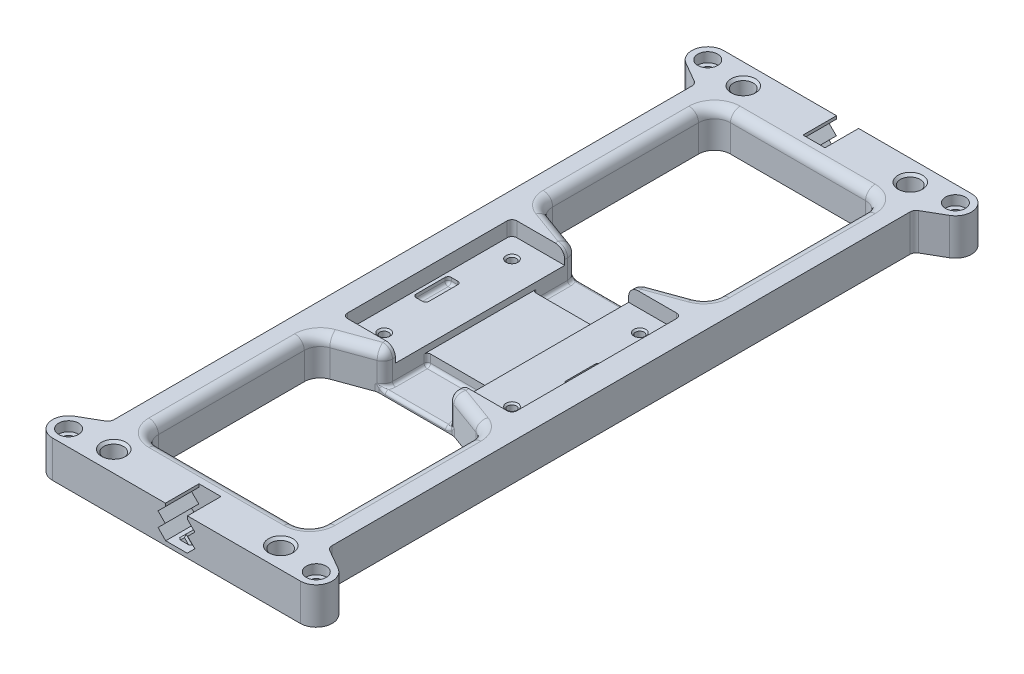
SolidWorks part; units mm, degrees
ref_plane "Front Plane" through (0, 0, 0) normal (0, 0, 1) x (1, 0, 0)
ref_plane "Top Plane" through (0, 0, 0) normal (0, 1, 0) x (1, 0, 0)
ref_plane "Right Plane" through (0, 0, 0) normal (1, 0, 0) x (0, 0, -1)
sketch "Sketch1" plane through (0, 0, 0) normal (0, 1, 0) x (1, 0, 0)
  line L0 (0, 0) -> (0, 90) construction
  line L1 (34.125, 90) -> (-34.125, 90) construction
  line L2 (-34.125, 90) -> (-34.125, 0)
  line L3 (-34.125, 0) -> (34.125, 0)
  line L4 (-34.125, 90) -> (-34.125, 103)
  line L5 (-32.125, 105) -> (32.125, 105)
  line L6 (0, 105) -> (0, 90) construction
  line L7 (34.125, 90) -> (34.125, 103)
  line L8 (34.125, 90) -> (34.125, 0)
  line L14 (-34.125, 93) -> (34.125, 93) construction
  circle A1 centre (-26.125, 98.5) radius 3.075 construction
  circle A2 centre (26.125, 98.5) radius 3.075 construction
  arc A10 (34.125, 103) -> (32.125, 105) centre (32.125, 103) ccw
  arc A11 (-34.125, 103) -> (-32.125, 105) centre (-32.125, 103) cw
  point P42 (34.125, 105)
  point P45 (-34.125, 105)
  dimension "D3" = 6.15
  dimension "D4" = 2
  dimension "D1" = 34.125
  dimension "D2" = 90
  dimension "D6" = 8
  dimension "D7" = 8.5
  dimension "D8" = 12
  dimension "D9" = 3
  dimension "D11" = 105
extrude "Boss-Extrude1" add sketch "Sketch1" along normal blind 11.5
sketch "Sketch3" plane through (0, 11.5, 0) normal (0, 1, 0) x (1, 0, 0)
  line L0 (0, 0) -> (-34.125, 0) construction
  line L2 (0, 0) -> (0, 105) construction
  line L3 (32.125, 105) -> (-32.125, 105) construction
  line L4 (3.96, -16.3) -> (3.96, 16.3)
  line L5 (-2.46, -17.8) -> (2.46, -17.8)
  line L6 (-3.96, 16.3) -> (-3.96, -16.3)
  line L7 (2.46, 17.8) -> (-2.46, 17.8)
  line L8 (0, 17.8) -> (0, -17.8) construction
  arc A0 (-2.46, 17.8) -> (-3.96, 16.3) centre (-2.46, 16.3) ccw
  arc A1 (3.96, 16.3) -> (2.46, 17.8) centre (2.46, 16.3) ccw
  arc A2 (2.46, -17.8) -> (3.96, -16.3) centre (2.46, -16.3) ccw
  arc A3 (-3.96, -16.3) -> (-2.46, -17.8) centre (-2.46, -16.3) ccw
  point P9 (0, 0)
  point P23 (0, 0)
  dimension "D2" = 1.5
  dimension "D1" = 35.6
  dimension "D3" = 7.92
sketch "Sketch4" plane through (0, 11.5, 0) normal (0, 1, 0) x (1, 0, 0)
  circle A2 centre (26.125, 98.5) radius 3.075 construction
  circle A5 centre (-26.125, 98.5) radius 3.075 construction
  circle A10 centre (26.125, 98.5) radius 3.075
  circle A13 centre (-26.125, 98.5) radius 3.075
extrude "Cut-Extrude1" cut sketch "Sketch4" against normal blind 6
sketch "Sketch41" plane through (0, 0, -105) normal (0, 0, -1) x (-1, 0, 0)
  line L0 (5.55, 3.75) -> (3.3, 6) construction
  line L1 (5.55, 3.75) -> (3.3, 1.5) construction
  line L2 (0, 11.5) -> (0, 1.5) construction
  line L3 (0, 1.5) -> (3.3, 1.5) construction
  line L4 (3.3, 6) -> (5.55, 8.25) construction
  line L5 (3.3, 6) -> (3.3, 1.5) construction
  line L6 (5.55, 8.25) -> (3.3, 10.5) construction
  line L7 (3.3, 6) -> (3.3, 10.5) construction
  line L8 (5.55, 3.75) -> (5.55, 8.25) construction
  line L9 (3.3, 10.5) -> (3.3, 11.5) construction
  line L10 (3.3, 1.5) -> (5.55, 1.5) construction
  line L11 (5.55, 1.5) -> (5.55, 3.75) construction
  line L12 (5.55, 3.75) -> (3.3, 3.75) construction
  line L13 (5.55, 8.25) -> (3.3, 8.25) construction
  line L14 (3.3, 6) -> (5.55, 6) construction
  line L15 (-3.3, 11.5) -> (3.3, 11.5)
  line L16 (3.3621, 1.35) -> (-3.3621, 1.35)
  line L17 (0, 1.35) -> (0, 1.5) construction
  line L18 (-3.3, 11.5) -> (-3.45, 11.5)
  line L19 (-3.45, 10.5621) -> (-3.45, 11.5)
  line L20 (3.45, 10.5621) -> (3.45, 11.5)
  line L21 (5.7621, 8.25) -> (3.45, 10.5621)
  line L22 (3.5121, 6) -> (5.7621, 8.25)
  line L23 (5.7621, 3.75) -> (3.5121, 6)
  line L24 (5.7621, 3.75) -> (3.3621, 1.35)
  line L25 (3.3, 11.5) -> (3.45, 11.5)
  line L26 (-5.7621, 8.25) -> (-3.45, 10.5621)
  line L27 (-3.5121, 6) -> (-5.7621, 8.25)
  line L28 (-5.7621, 3.75) -> (-3.5121, 6)
  line L29 (-5.7621, 3.75) -> (-3.3621, 1.35)
  line L30 (-32.125, 11.5) -> (32.125, 11.5) construction
  dimension "D1" = 1
  dimension "D2" = 45
  dimension "D3" = 45
  dimension "D4" = 45
  dimension "D5" = 45
  dimension "D6" = 3.3
  dimension "D7" = 10
  dimension "D8" = 0.15
  dimension "D9" = 0.15
  dimension "D10" = 0.15
  dimension "D11" = 0.15
  dimension "D12" = 0.15
  dimension "D13" = 0.15
extrude "Cut-Extrude31" cut sketch "Sketch41" against normal blind 10.5
sketch "Sketch42" plane through (0, 0, -94.5) normal (0, 0, -1) x (-1, 0, 0)
  line L0 (0, 1.35) -> (0, 3.35) construction
  line L1 (-3.3621, 1.35) -> (3.3621, 1.35) construction
  line L2 (0, 3.35) -> (2, 1.35)
  line L3 (2, 1.35) -> (-2, 1.35)
  line L4 (0, 3.35) -> (-2, 1.35)
  dimension "D1" = 45
  dimension "D2" = 2
extrude "Boss-Extrude9" add sketch "Sketch42" along normal blind 8
chamfer "Chamfer7" distance 0.5 angle 45 2 edges at (1, 2.35, -102.5) (-1, 2.35, -102.5)
mirror "Mirror1" about plane through (-34.125, 11.5, 0) normal (0, 0, -1) of "Boss-Extrude1", "Cut-Extrude1", "Cut-Extrude31", "Boss-Extrude9", "Chamfer7"
sketch "Sketch28" plane through (0, 11.5, 0) normal (0, 1, 0) x (1, 0, 0)
  line L1 (-26, 26) -> (26, 26) construction
  line L2 (-26, 26) -> (-26, -26) construction
  line L3 (-26, -26) -> (26, -26) construction
  line L4 (26, 26) -> (26, -26) construction
  line L5 (-26, 26) -> (26, -26) construction
  line L6 (-26, -26) -> (26, 26) construction
  line L7 (-25, 26.5) -> (25, 26.5)
  line L8 (-26.5, 25) -> (-26.5, -25)
  line L9 (-25, -26.5) -> (25, -26.5)
  line L10 (26.5, 25) -> (26.5, -25)
  line L11 (-26.5, 26.5) -> (26.5, -26.5) construction
  line L12 (-26.5, -26.5) -> (26.5, 26.5) construction
  arc A0 (-25, -26.5) -> (-26.5, -25) centre (-25, -25) cw
  arc A1 (25, -26.5) -> (26.5, -25) centre (25, -25) ccw
  arc A2 (25, 26.5) -> (26.5, 25) centre (25, 25) cw
  arc A3 (-25, 26.5) -> (-26.5, 25) centre (-25, 25) ccw
  point P0 (0, 0)
  point P6 (0, 0)
  dimension "D4" = 1.5
  dimension "D1" = 52
  dimension "D2" = 0.5
  dimension "D3" = 0.5
extrude "Cut-Extrude21" cut sketch "Sketch28" against normal blind 4.6
sketch "Sketch36" plane through (0, 6.9, 0) normal (0, 1, 0) x (1, 0, 0)
  line L2 (-26, 26) -> (-26, -26) construction
  line L3 (-26, 26) -> (26, 26) construction
  circle A0 centre (-20, 20) radius 1.35
  circle A1 centre (20, 20) radius 1.35
  circle A2 centre (20, -20) radius 1.35
  circle A3 centre (-20, -20) radius 1.35
  point P15 (0, 0)
  dimension "D3" = 2.7
  dimension "D1" = 6
  dimension "D2" = 6
  dimension "D4" = 4
extrude "Cut-Extrude28" cut sketch "Sketch36" against normal blind 5
chamfer "Chamfer6" distance 0.5 angle 45 4 edges at (-20, 6.9, 21.35) (20, 6.9, 21.35) (20, 6.9, -18.65) (-20, 6.9, -18.65)
sketch "Sketch29" plane through (0, 6.9, 0) normal (0, 1, 0) x (1, 0, 0)
  line L0 (0, 0) -> (26.5, 0) construction
  line L5 (0, 0) -> (0, -26.5) construction
  line L6 (-25, -26.5) -> (25, -26.5) construction
  line L7 (26.5, -25) -> (26.5, 25) construction
  line L8 (-10, 26.5) -> (10, 16.5) construction
  line L9 (-10, 16.5) -> (10, 26.5) construction
  line L10 (-10, -16.5) -> (10, -16.5)
  line L11 (-10, -16.5) -> (-10, -26.5)
  line L12 (-10, -26.5) -> (10, -26.5)
  line L13 (10, -16.5) -> (10, -26.5)
  line L14 (-10, -16.5) -> (10, -26.5) construction
  line L15 (-10, -26.5) -> (10, -16.5) construction
  line L16 (10, 16.5) -> (10, 26.5)
  line L17 (-10, 26.5) -> (10, 26.5)
  line L18 (-10, 16.5) -> (-10, 26.5)
  line L19 (-10, 16.5) -> (10, 16.5)
  point P4 (0, -21.5)
  point P17 (0, 21.5)
  dimension "D1" = 20
  dimension "D2" = 10
extrude "Cut-Extrude22" cut sketch "Sketch29" against normal blind 5.5
sketch "Sketch25" plane through (0, 0, 0) normal (0, -1, 0) x (1, 0, 0)
  line L0 (0, 0) -> (34.125, 0) construction
  line L1 (34.125, 103) -> (34.125, -103) construction
  line L2 (0, 0) -> (0, 105) construction
  line L4 (41.25, 95.6699) -> (35.125, 92.1336)
  line L5 (38.75, 100) -> (34.125, 100) construction
  line L6 (34.125, 90.4016) -> (34.125, 103)
  line L8 (32.125, 105) -> (38.75, 105)
  line L9 (-38.75, 100) -> (-34.125, 100) construction
  line L10 (-32.125, 105) -> (-38.75, 105)
  line L11 (-34.125, 90.4016) -> (-34.125, 103)
  line L12 (-41.25, 95.6699) -> (-35.125, 92.1336)
  line L13 (-38.75, -100) -> (-34.125, -100) construction
  line L14 (38.75, -100) -> (34.125, -100) construction
  line L15 (-41.25, -95.6699) -> (-35.125, -92.1336)
  line L16 (-34.125, -90.4016) -> (-34.125, -103)
  line L17 (-32.125, -105) -> (-38.75, -105)
  line L18 (32.125, -105) -> (38.75, -105)
  line L19 (34.125, -90.4016) -> (34.125, -103)
  line L20 (41.25, -95.6699) -> (35.125, -92.1336)
  line L21 (32.125, 105) -> (-32.125, 105) construction
  circle A0 centre (38.75, 100) radius 1.7
  arc A1 (41.25, 95.6699) -> (38.75, 105) centre (38.75, 100) ccw
  arc A2 (35.125, 92.1336) -> (34.125, 90.4016) centre (36.125, 90.4016) ccw
  arc A17 (34.125, 103) -> (32.125, 105) centre (32.125, 103) ccw
  arc A18 (-34.125, 103) -> (-32.125, 105) centre (-32.125, 103) cw
  arc A19 (-35.125, 92.1336) -> (-34.125, 90.4016) centre (-36.125, 90.4016) cw
  arc A20 (-41.25, 95.6699) -> (-38.75, 105) centre (-38.75, 100) cw
  circle A21 centre (-38.75, 100) radius 1.7
  circle A22 centre (-38.75, -100) radius 1.7
  arc A23 (-41.25, -95.6699) -> (-38.75, -105) centre (-38.75, -100) ccw
  arc A24 (-35.125, -92.1336) -> (-34.125, -90.4016) centre (-36.125, -90.4016) ccw
  arc A25 (-34.125, -103) -> (-32.125, -105) centre (-32.125, -103) ccw
  arc A26 (34.125, -103) -> (32.125, -105) centre (32.125, -103) cw
  arc A27 (35.125, -92.1336) -> (34.125, -90.4016) centre (36.125, -90.4016) cw
  arc A28 (41.25, -95.6699) -> (38.75, -105) centre (38.75, -100) cw
  circle A29 centre (38.75, -100) radius 1.7
  arc A30 (34.125, 103) -> (32.125, 105) centre (32.125, 103) ccw construction
  dimension "D1" = 3.4
  dimension "D2" = 10
  dimension "D6" = 2
  dimension "D3" = 4.625
  dimension "D5" = 60
extrude "Boss-Extrude7" add sketch "Sketch25" against normal up to surface (11.5 mm away) up to face at (0, 11.5, 0)
sketch "Sketch27" plane through (0, 11.5, 0) normal (0, 1, 0) x (1, 0, 0)
  circle A4 centre (-38.75, -100) radius 3.1
  circle A5 centre (38.75, -100) radius 3.1
  circle A6 centre (-38.75, 100) radius 3.1
  circle A7 centre (38.75, 100) radius 3.1
  dimension "D1" = 6.2
extrude "Cut-Extrude20" cut sketch "Sketch27" against normal blind 3
sketch "Sketch37" plane through (0, 6.9, 0) normal (0, 1, 0) x (1, 0, 0)
  line L0 (34.125, 0) -> (0, 0) construction
  line L1 (34.125, -90.4016) -> (34.125, 90.4016) construction
  line L2 (0, 0) -> (-34.125, 0) construction
  line L3 (26.5, -25) -> (26.5, 25) construction
  line L4 (24.5, 5.5) -> (22.5, 5.5)
  line L5 (25.5, 4.5) -> (25.5, -4.5)
  line L6 (24.5, -5.5) -> (22.5, -5.5)
  line L7 (21.5, 4.5) -> (21.5, -4.5)
  line L8 (25.5, 5.5) -> (21.5, -5.5) construction
  line L9 (25.5, -5.5) -> (21.5, 5.5) construction
  line L10 (0, 0) -> (0, 26.5) construction
  line L11 (-10, 16.5) -> (10, 16.5) construction
  line L12 (-24.5, -5.5) -> (-22.5, -5.5)
  line L13 (-25.5, 4.5) -> (-25.5, -4.5)
  line L14 (-24.5, 5.5) -> (-22.5, 5.5)
  line L15 (-21.5, 4.5) -> (-21.5, -4.5)
  line L21 (10, 16.5) -> (10, -16.5)
  line L23 (25, 26.5) -> (-25, 26.5) construction
  line L24 (-10, 16.5) -> (10, 16.5)
  line L25 (-10, 16.5) -> (-10, -16.5)
  line L26 (-10, -16.5) -> (10, -16.5)
  arc A0 (22.5, -5.5) -> (21.5, -4.5) centre (22.5, -4.5) cw
  arc A1 (25.5, -4.5) -> (24.5, -5.5) centre (24.5, -4.5) cw
  arc A2 (22.5, 5.5) -> (21.5, 4.5) centre (22.5, 4.5) ccw
  arc A3 (24.5, 5.5) -> (25.5, 4.5) centre (24.5, 4.5) cw
  arc A4 (-22.5, 5.5) -> (-21.5, 4.5) centre (-22.5, 4.5) cw
  arc A5 (-24.5, 5.5) -> (-25.5, 4.5) centre (-24.5, 4.5) ccw
  arc A6 (-22.5, -5.5) -> (-21.5, -4.5) centre (-22.5, -4.5) ccw
  arc A7 (-25.5, -4.5) -> (-24.5, -5.5) centre (-24.5, -4.5) ccw
  point P5 (23.5, 0)
  point P54 (10, 0)
  point P56 (-10, 0)
  dimension "D4" = 1
  dimension "D1" = 11
  dimension "D2" = 4
  dimension "D3" = 3
extrude "Cut-Extrude29" cut sketch "Sketch37" against normal blind 2
fillet "Fillet20" radius 1 16 edges at (25.2071, 4.9, -5.2071) (25.5, 4.9, 0) (25.2071, 4.9, 5.2071) (23.5, 4.9, 5.5) (21.7929, 4.9, 5.2071) (21.5, 4.9, 0) (21.7929, 4.9, -5.2071) (-21.7929, 4.9, -5.2071) (-21.5, 4.9, 0) (-21.7929, 4.9, 5.2071) (-23.5, 4.9, 5.5) (-25.2071, 4.9, 5.2071) (-25.5, 4.9, 0) (-25.2071, 4.9, -5.2071) (23.5, 4.9, -5.5) (-23.5, 4.9, -5.5)
sketch "Sketch38" plane through (0, 11.5, 0) normal (0, 1, 0) x (1, 0, 0)
  line L0 (11.9739, -30.2185) -> (22.8351, -34.1716)
  line L1 (26.125, -38.8701) -> (26.125, -84.5)
  line L2 (21.125, -89.5) -> (-21.125, -89.5)
  line L3 (0, -89.5) -> (0, -26.5) construction
  line L4 (-10, -26.5) -> (10, -26.5) construction
  line L6 (34.125, -90.4016) -> (34.125, 90.4016) construction
  line L7 (-3.45, -94.5) -> (3.45, -94.5) construction
  line L9 (-25, -26.5) -> (25, -26.5) construction
  line L12 (0, 0) -> (34.125, 0) construction
  line L13 (0, 89.5) -> (0, 26.5) construction
  line L20 (10, -27.3994) -> (10, -26.5)
  line L21 (10, -26.5) -> (25, -26.5) construction
  line L22 (10, -26.5) -> (-10, -26.5)
  line L23 (10, -26.5) -> (10, 26.5) construction
  line L24 (-10, -27.3994) -> (-10, -26.5)
  line L25 (-26.125, -38.8701) -> (-26.125, -84.5)
  line L26 (-11.9739, -30.2185) -> (-22.8351, -34.1716)
  line L27 (-11.9739, 30.2185) -> (-22.8351, 34.1716)
  line L28 (-26.125, 38.8701) -> (-26.125, 84.5)
  line L29 (-10, 27.3994) -> (-10, 26.5)
  line L30 (10, 26.5) -> (-10, 26.5)
  line L31 (10, 27.3994) -> (10, 26.5)
  line L32 (21.125, 89.5) -> (-21.125, 89.5)
  line L33 (26.125, 38.8701) -> (26.125, 84.5)
  line L34 (11.9739, 30.2185) -> (22.8351, 34.1716)
  arc A0 (26.125, -38.8701) -> (22.8351, -34.1716) centre (21.125, -38.8701) ccw
  arc A1 (26.125, -84.5) -> (21.125, -89.5) centre (21.125, -84.5) cw
  arc A8 (11.9739, -30.2185) -> (10, -27.3994) centre (13, -27.3994) cw
  arc A9 (-11.9739, -30.2185) -> (-10, -27.3994) centre (-13, -27.3994) ccw
  arc A10 (-26.125, -84.5) -> (-21.125, -89.5) centre (-21.125, -84.5) ccw
  arc A11 (-26.125, -38.8701) -> (-22.8351, -34.1716) centre (-21.125, -38.8701) cw
  arc A12 (-26.125, 38.8701) -> (-22.8351, 34.1716) centre (-21.125, 38.8701) ccw
  arc A13 (-26.125, 84.5) -> (-21.125, 89.5) centre (-21.125, 84.5) cw
  arc A14 (-11.9739, 30.2185) -> (-10, 27.3994) centre (-13, 27.3994) cw
  arc A15 (11.9739, 30.2185) -> (10, 27.3994) centre (13, 27.3994) ccw
  arc A16 (26.125, 84.5) -> (21.125, 89.5) centre (21.125, 84.5) ccw
  arc A17 (26.125, 38.8701) -> (22.8351, 34.1716) centre (21.125, 38.8701) cw
  point P49 (10, -29.5)
  point P60 (-10, -29.5)
  point P67 (-10, 29.5)
  point P68 (10, 29.5)
  dimension "D4" = 5
  dimension "D6" = 3
  dimension "D1" = 5
  dimension "D2" = 8
  dimension "D3" = 20
  dimension "D5" = 3
extrude "Cut-Extrude30" cut sketch "Sketch38" against normal through all
sketch "Sketch39" plane through (0, 0, 0) normal (0, -1, 0) x (1, 0, 0)
  line L0 (0, 0) -> (34.125, 0) construction
  line L1 (34.125, 90.4016) -> (34.125, -90.4016) construction
  line L2 (-11.9739, 30.2185) -> (11.9739, 30.2185)
  line L3 (10, 27.3994) -> (10, 26.5) construction
  line L4 (10, 26.5) -> (-10, 26.5) construction
  line L5 (-10, 26.5) -> (-10, 27.3994) construction
  line L6 (10, 27.3994) -> (10, 26.5)
  line L7 (10, 26.5) -> (-10, 26.5)
  line L8 (-10, 26.5) -> (-10, 27.3994)
  line L9 (-10, -26.5) -> (-10, -27.3994)
  line L10 (10, -26.5) -> (-10, -26.5)
  line L11 (10, -27.3994) -> (10, -26.5)
  line L12 (-11.9739, -30.2185) -> (11.9739, -30.2185)
  arc A0 (11.9739, 30.2185) -> (10, 27.3994) centre (13, 27.3994) ccw construction
  arc A1 (-10, 27.3994) -> (-11.9739, 30.2185) centre (-13, 27.3994) ccw construction
  arc A2 (11.9739, 30.2185) -> (10, 27.3994) centre (13, 27.3994) ccw
  arc A3 (-10, 27.3994) -> (-11.9739, 30.2185) centre (-13, 27.3994) ccw
  arc A4 (-10, -27.3994) -> (-11.9739, -30.2185) centre (-13, -27.3994) cw
  arc A5 (11.9739, -30.2185) -> (10, -27.3994) centre (13, -27.3994) cw
extrude "Boss-Extrude8" add sketch "Sketch39" against normal up to surface (1.4 mm away) up to face at (0, 1.4, 21.5)
fillet "Fillet21" radius 1 14 edges at (0, 1.4, -16.5) (0, 1.4, 16.5) (-10.5425, 1.4, -29.1201) (10.5425, 1.4, -29.1201) (-10.5425, 1.4, 29.1201) (10.5425, 1.4, 29.1201) (-10, 1.4, -21.9497) (-10, 3.15, -16.5) (10, 1.4, -21.9497) (10, 3.15, -16.5) (-10, 3.15, 16.5) (-10, 1.4, 21.9497) (10, 3.15, 16.5) (10, 1.4, 21.9497)
fillet "Fillet22" radius 3 26 edges at (10, 11.5, -26.9497) (10.5425, 11.5, -29.1201) (17.4045, 11.5, -32.195) (25.2208, 11.5, -36.0022) (26.125, 11.5, -61.685) (24.6605, 11.5, -88.0355) (0, 11.5, -89.5) (-24.6605, 11.5, -88.0355) (-26.125, 11.5, -61.685) (-25.2208, 11.5, -36.0022) (-10, 11.5, -26.9497) (-10.5425, 11.5, -29.1201) (-10, 11.5, 26.9497) (-10.5425, 11.5, 29.1201) (10, 11.5, 26.9497) (10.5425, 11.5, 29.1201) (17.4045, 11.5, 32.195) (25.2208, 11.5, 36.0022) (26.125, 11.5, 61.685) (24.6605, 11.5, 88.0355) (0, 11.5, 89.5) (-24.6605, 11.5, 88.0355) (-26.125, 11.5, 61.685) (-25.2208, 11.5, 36.0022) (-17.4045, 11.5, -32.195) (-17.4045, 11.5, 32.195)
fillet "Fillet24" radius 3 4 edges at (-11.9739, 1.2, 30.2185) (11.9739, 1.2, 30.2185) (11.9739, 1.2, -30.2185) (-11.9739, 1.2, -30.2185)
fillet "Fillet25" radius 1 10 edges at (0, 1.4, 30.2185) (0, 1.4, -30.2185) (-12.1079, 2.1665, -30.2926) (-10.8141, 1.4985, -30.2185) (12.1976, 2.1847, -30.3144) (10.9036, 1.5265, -30.2185) (12.1079, 2.1665, 30.2926) (10.8141, 1.4985, 30.2185) (-12.1976, 2.1847, 30.3144) (-10.9036, 1.5265, 30.2185)
chamfer "Chamfer8" distance 0.75 angle 45 4 edges at (26.125, 11.5, -95.425) (-26.125, 11.5, -95.425) (-26.125, 11.5, 95.425) (26.125, 11.5, 95.425)
equation "\"D3@Sketch28\"=\"D2@Sketch28\""
equation "\"D2@Sketch36\"=\"D1@Sketch36\""
